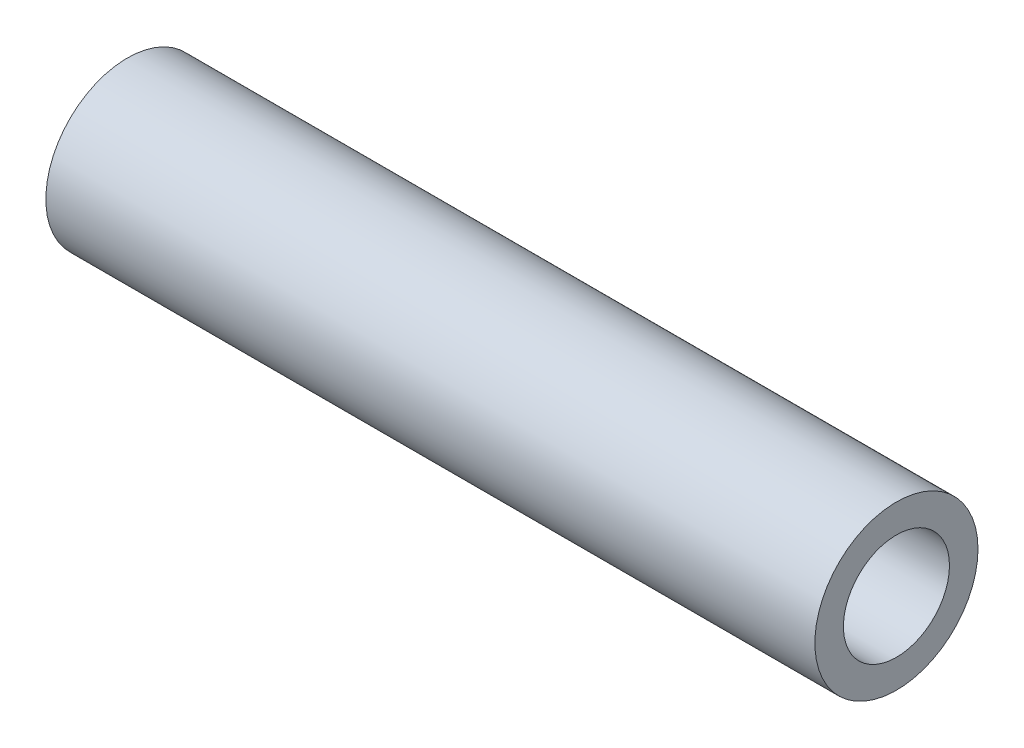
SolidWorks part; units mm, degrees
ref_plane "Front Plane" through (0, 0, 0) normal (0, 0, 1) x (1, 0, 0)
ref_plane "Top Plane" through (0, 0, 0) normal (0, 1, 0) x (1, 0, 0)
ref_plane "Right Plane" through (0, 0, 0) normal (1, 0, 0) x (0, 0, -1)
sketch "Sketch1" plane through (0, 0, 0) normal (1, 0, 0) x (0, 0, -1)
  circle A0 centre (0, 0) radius 3.5
  circle A1 centre (0, 0) radius 2.275
  dimension "D1" = 4.55
  dimension "D2" = 7
extrude "Boss-Extrude1" add sketch "Sketch1" along normal blind 33
